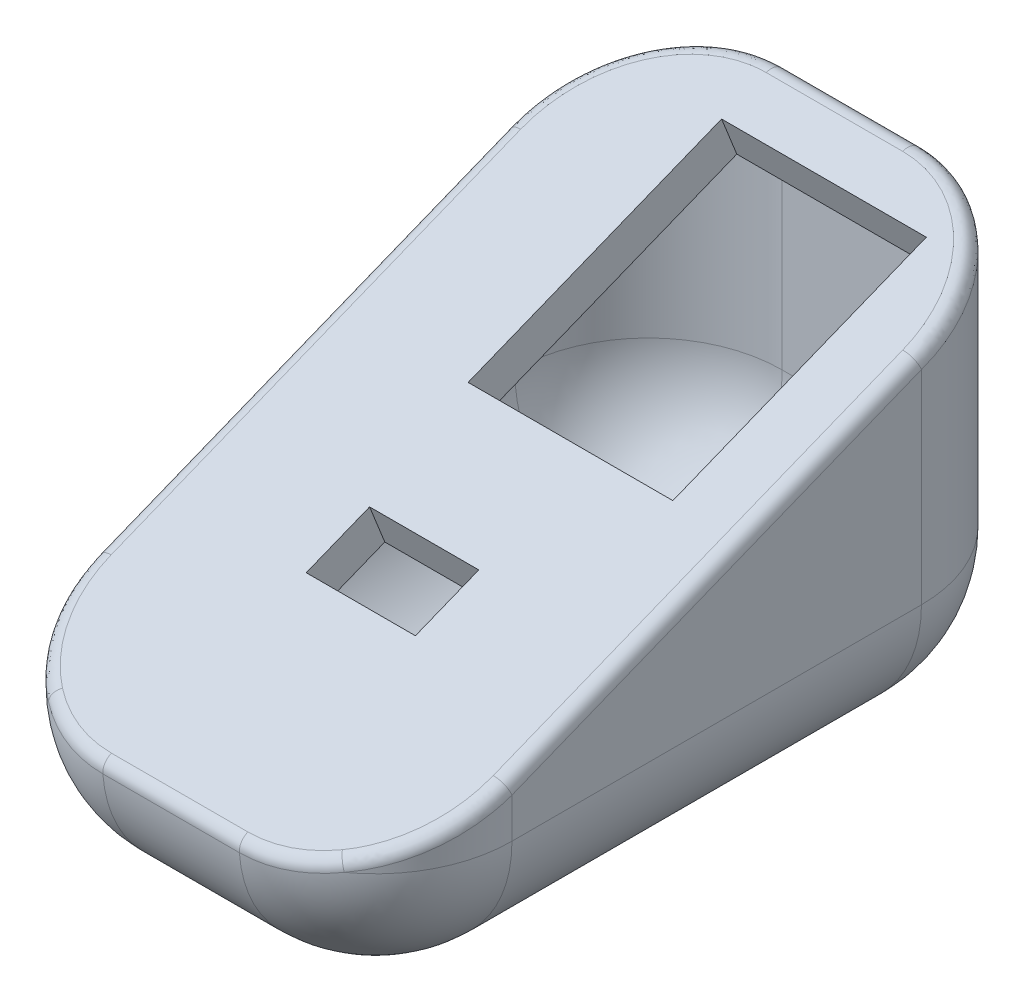
SolidWorks part; units mm, degrees
ref_plane "Front Plane" through (0, 0, 0) normal (0, 0, 1) x (1, 0, 0)
ref_plane "Top Plane" through (0, 0, 0) normal (0, 1, 0) x (1, 0, 0)
ref_plane "Right Plane" through (0, 0, 0) normal (1, 0, 0) x (0, 0, -1)
sketch "Sketch1" plane through (0, 0, 0) normal (1, 0, 0) x (0, 0, -1)
  line L0 (0, 313.7838) -> (0, 13.7838)
  line L1 (0, 13.7838) -> (-500, 13.7838)
  line L2 (-500, 13.7838) -> (-500, 113.7838)
  line L3 (-500, 113.7838) -> (0, 313.7838)
  dimension "D1" = 300
  dimension "D2" = 500
  dimension "D3" = 100
extrude "Boss-Extrude2" add sketch "Sketch1" along normal mid plane 300
fillet "Fillet2" radius 100 4 edges at (-150, 163.7838, 0) (150, 163.7838, 0) (-150, 63.7838, 500) (150, 63.7838, 500)
fillet "Fillet3" radius 100 8 edges at (120.7107, 13.7838, 470.7107) (0, 13.7838, 500) (-120.7107, 13.7838, 470.7107) (-150, 13.7838, 250) (-120.7107, 13.7838, 29.2893) (0, 13.7838, 0) (120.7107, 13.7838, 29.2893) (150, 13.7838, 250)
sketch "Sketch2" plane through (0, 270.5033, 108.2013) normal (0, 0.9285, 0.3714) x (1, 0, 0)
  line L0 (50, -421.9801) -> (-50, -421.9801) construction
  line L1 (-40, -221.9801) -> (40, -221.9801)
  line L2 (-40, -221.9801) -> (-40, -271.9801)
  line L3 (-40, -271.9801) -> (40, -271.9801)
  line L4 (40, -221.9801) -> (40, -271.9801)
  line L5 (0, -271.9801) -> (0, -221.9801) construction
  line L6 (-40, -246.9801) -> (40, -246.9801) construction
  line L7 (150, 8.8331) -> (150, -314.2768) construction
  line L12 (-50, 66.5364) -> (100, 66.5364)
  line L13 (-50, 66.5364) -> (-50, -133.4636)
  line L14 (-50, -133.4636) -> (100, -133.4636)
  line L15 (100, 66.5364) -> (100, -133.4636)
  line L16 (25, -133.4636) -> (25, 66.5364) construction
  line L17 (-50, -33.4636) -> (100, -33.4636) construction
  line L19 (50, 116.5364) -> (-50, 116.5364) construction
  point P0 (0, -246.9801)
  point P6 (25, -33.4636)
  point P12 (25, -58.8466)
  dimension "D1" = 50
  dimension "D2" = 80
  dimension "D3" = 150
  dimension "D4" = 150
  dimension "D5" = 200
  dimension "D6" = 50
  dimension "D7" = 50
extrude "Cut-Extrude3" cut sketch "Sketch2" against normal blind 30
fillet "Fillet5" radius 10 8 edges at (-120.7107, 125.4995, 470.7107) (-150, 213.7838, 250) (-120.7107, 302.0681, 29.2893) (0, 313.7838, 0) (120.7107, 302.0681, 29.2893) (0, 113.7838, 500) (120.7107, 125.4995, 470.7107) (150, 213.7838, 250)
shell "Shell1" thickness 2 removed face at (0, 150.9229, 326.3749) removed face at (25, 230.2209, 128.1298)
